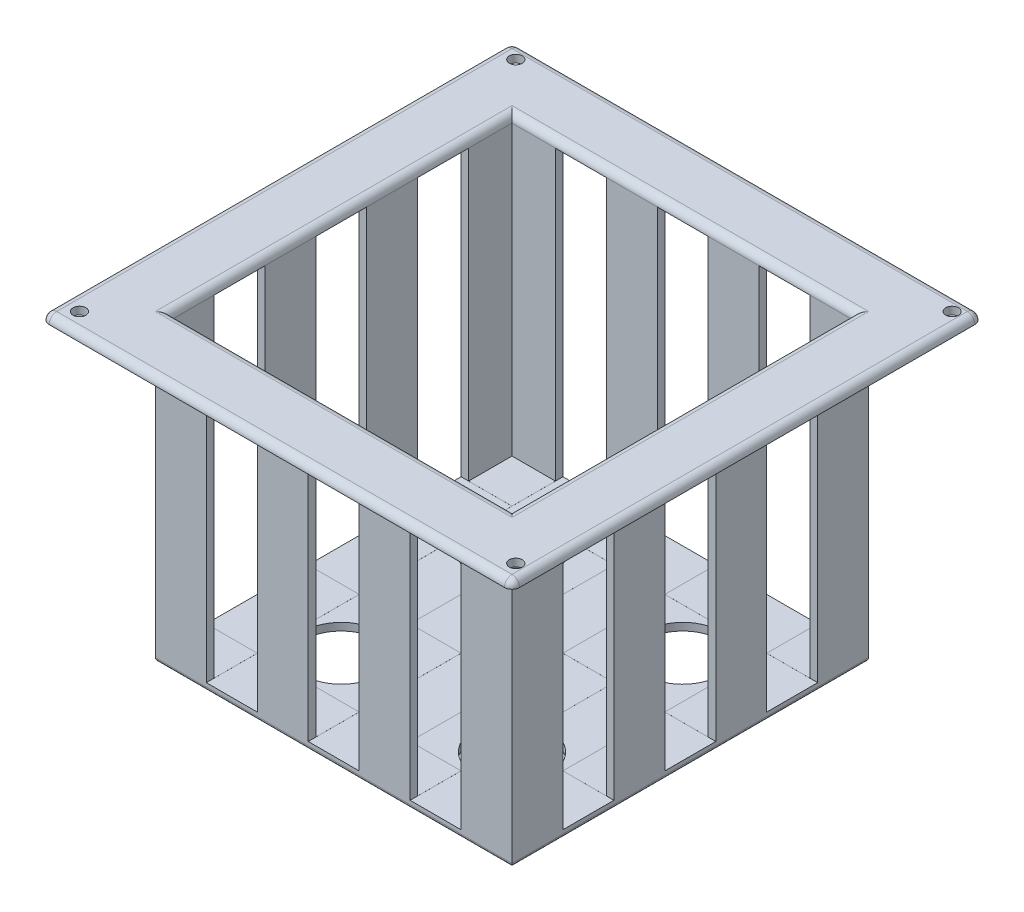
SolidWorks part; units mm, degrees
ref_plane "前视基准面" through (0, 0, 0) normal (0, 0, 1) x (1, 0, 0)
ref_plane "上视基准面" through (0, 0, 0) normal (0, 1, 0) x (1, 0, 0)
ref_plane "右视基准面" through (0, 0, 0) normal (1, 0, 0) x (0, 0, -1)
sketch "草图1" plane through (0, 0, 0) normal (0, 1, 0) x (1, 0, 0)
  line L0 (-44.8787, 74.0445) -> (49.1213, 74.0445)
  line L1 (-42.8787, 72.0445) -> (47.1213, 72.0445)
  line L2 (-42.8787, 72.0445) -> (-42.8787, -17.9555)
  line L3 (-42.8787, -17.9555) -> (47.1213, -17.9555)
  line L4 (47.1213, 72.0445) -> (47.1213, -17.9555)
  line L5 (49.1213, 74.0445) -> (49.1213, -19.9555)
  line L6 (-44.8787, -19.9555) -> (49.1213, -19.9555)
  line L7 (-44.8787, 74.0445) -> (-44.8787, -19.9555)
  line L8 (-59.8787, 89.0445) -> (64.1213, 89.0445)
  line L9 (64.1213, 89.0445) -> (64.1213, -34.9555)
  line L10 (-59.8787, -34.9555) -> (64.1213, -34.9555)
  line L11 (-59.8787, 89.0445) -> (-59.8787, -34.9555)
  dimension "D1" = 2
  dimension "D2" = 15
extrude "凸台-拉伸1" add sketch "草图1" against normal blind 80 contours L5 L6 L7 L0
extrude "切除-拉伸1" cut sketch "草图1<3>" against normal blind 78 contours L3 L4 L1 L2
sketch "草图1<3>" plane through (0, 0, 0) normal (0, 1, 0) x (1, 0, 0) same geometry as "草图1"
ref_plane "基准面4" through (0, 10, 0) normal (0, 1, 0) x (1, 0, 0)
extrude "凸台-拉伸2" add sketch "草图1<5>" against normal blind 2 contours L0 L5 L6 L7 | L8 L9 L10 L11
sketch "草图1<5>" plane through (0, 0, 0) normal (0, 1, 0) x (1, 0, 0) same geometry as "草图1"
fillet "圆角1" radius 2 4 edges at (2.1213, 0, 17.9555) (47.1213, 0, -27.0445) (2.1213, 0, -72.0445) (-42.8787, 0, -27.0445)
sketch3d "3D草图1"
  line L0 (49.1213, -80, 19.9555) -> (49.1213, -78, 19.9555) construction
  line L1 (49.1213, -80, 19.9555) -> (49.1213, -2, 19.9555) construction
  line L2 (49.1213, -78, 19.9555) -> (49.1213, -78.0094, -74.0445) construction
  line L3 (49.1213, -80, -74.0445) -> (49.1213, -2, -74.0445) construction
  line L4 (49.1213, -78.0094, -74.0445) -> (-44.8787, -78.0094, -74.0445) construction
  line L5 (-44.8787, -80, -74.0445) -> (-44.8787, -2, -74.0445) construction
  line L6 (-44.8787, -78.0094, -74.0445) -> (-44.8787, -78.0094, 19.9555) construction
  line L7 (-44.8787, -80, 19.9555) -> (-44.8787, -2, 19.9555) construction
  line L8 (-44.8787, -78.0094, 19.9555) -> (49.1213, -78, 19.9555) construction
ref_point "点1"
ref_point "点2"
ref_point "点3"
ref_point "点4"
ref_point "点5"
ref_point "点6"
sketch "草图5" plane through (49.1213, 0, 0) normal (1, 0, 0) x (0, 0, -1)
  line L0 (-19.9555, -2) -> (-6.5269, -2)
  line L1 (-6.5269, -78.0013) -> (-6.5269, -2)
  line L2 (74.0445, -2) -> (-19.9555, -2) construction
  line L3 (6.9017, -78.0027) -> (6.9017, -2)
  line L4 (20.3302, -78.004) -> (20.3302, -2)
  line L5 (33.7588, -78.0053) -> (33.7588, -2)
  line L6 (47.1874, -78.0067) -> (47.1874, -2)
  line L7 (60.616, -78.008) -> (60.616, -2)
  line L8 (-6.5269, -78.0013) -> (6.9017, -78.0027)
  line L9 (6.9017, -78.0027) -> (20.3302, -78.004)
  line L10 (20.3302, -78.004) -> (33.7588, -78.0053)
  line L11 (33.7588, -78.0053) -> (47.1874, -78.0067)
  line L12 (47.1874, -78.0067) -> (60.616, -78.008)
  line L13 (60.616, -78.008) -> (74.0445, -78.0094)
  line L14 (74.0445, -78.0094) -> (74.0445, -2)
  line L15 (74.0445, -2) -> (60.616, -2)
  line L16 (60.616, -2) -> (47.1874, -2)
  line L17 (33.7588, -2) -> (20.3302, -2)
  line L18 (20.3302, -2) -> (6.9017, -2)
  line L19 (6.9017, -2) -> (-6.5269, -2)
  line L20 (-6.5269, -2) -> (-19.9555, -2)
  line L21 (-19.9555, -2) -> (-19.9555, -78)
  line L22 (6.9017, -2) -> (20.3302, -2)
  line L23 (33.7588, -2) -> (47.1874, -2)
extrude "切除-拉伸4" cut sketch "草图5" against normal through all contours L8 L1 L19 L3
extrude "切除-拉伸5" cut sketch "草图5<5>" against normal through all contours L4 L17 L5 L10
sketch "草图5<5>" plane through (49.1213, 0, 0) normal (1, 0, 0) x (0, 0, -1) same geometry as "草图5"
extrude "切除-拉伸6" cut sketch "草图5<6>" against normal through all contours L7 L16 L6 L12
sketch "草图5<6>" plane through (49.1213, 0, 0) normal (1, 0, 0) x (0, 0, -1) same geometry as "草图5"
ref_point "点7"
ref_point "点8"
ref_point "点9"
ref_point "点10"
ref_point "点11"
ref_point "点12"
sketch "草图6" plane through (0, 0, -74.0445) normal (0, 0, -1) x (-1, 0, 0)
  line L1 (-35.6927, -78.0094) -> (-35.6927, -2)
  line L2 (44.8787, -2) -> (-49.1213, -2) construction
  line L3 (-35.6927, -2) -> (-22.2641, -2)
  line L4 (-22.2641, -2) -> (-22.2641, -78.0094)
  line L5 (-22.2641, -78.0094) -> (-8.8356, -78.0094)
  line L6 (-8.8356, -78.0094) -> (-8.8356, -2)
  line L7 (-8.8356, -2) -> (4.593, -2)
  line L8 (4.593, -2) -> (4.593, -78.0094)
  line L9 (4.593, -78.0094) -> (18.0216, -78.0094)
  line L10 (18.0216, -78.0094) -> (18.0216, -2)
  line L11 (-35.6927, -78.0094) -> (-22.2641, -78.0094)
  line L12 (-22.2641, -2) -> (-8.8356, -2)
  line L13 (4.593, -2) -> (18.0216, -2)
  line L14 (18.0216, -78.0094) -> (31.4502, -78.0094)
  line L15 (31.4502, -78.0094) -> (31.4502, -2)
  line L16 (31.4502, -2) -> (18.0216, -2)
  line L17 (4.593, -78.0094) -> (-8.8356, -78.0094)
extrude "切除-拉伸7" cut sketch "草图6" against normal through all contours L3 L4 L11 L1
extrude "切除-拉伸8" cut sketch "草图6<3>" against normal through all contours L6 L7 L8 L17
sketch "草图6<3>" plane through (0, 0, -74.0445) normal (0, 0, -1) x (-1, 0, 0) same geometry as "草图6"
extrude "切除-拉伸9" cut sketch "草图6<4>" against normal through all both and the other way through all contours L15 L16 L10 L14
sketch "草图6<4>" plane through (0, 0, -74.0445) normal (0, 0, -1) x (-1, 0, 0) same geometry as "草图6"
ref_plane "基准面6" through (0, -78, 0) normal (0, -1, 0) x (-1, 0, 0)
sketch "草图8" plane through (0, -78, 0) normal (0, -1, 0) x (-1, 0, 0)
  line L0 (-49.1213, -19.9555) -> (44.825, 73.9908) construction
  line L1 (-2.1481, 27.0177) -> (42.8787, -17.9555) construction
  line L2 (42.8787, -17.9555) -> (-2.1481, 27.0177) construction
  line L3 (-2.1481, 27.0177) -> (-47.1213, 72.0445) construction
  circle A0 centre (-2.1481, 27.0177) radius 2.5
  circle A1 centre (-2.1481, 27.0177) radius 8
  circle A2 centre (20.3653, 4.5311) radius 10
  circle A3 centre (-24.6347, 49.5311) radius 10
  circle A4 centre (-24.6347, 4.5311) radius 10
  circle A5 centre (20.3653, 49.5311) radius 10
extrude "切除-拉伸13" cut sketch "草图8" along normal through all contours A0
extrude "切除-拉伸16" cut sketch "草图8<4>" along normal blind 1 contours A1
sketch "草图8<4>" plane through (0, -78, 0) normal (0, -1, 0) x (-1, 0, 0) same geometry as "草图8"
ref_point "点13"
ref_point "点14"
ref_point "点15"
extrude "切除-拉伸17" cut sketch "草图8<5>" along normal through all contours A2 | A3 | A4 | A5
sketch "草图8<5>" plane through (0, -78, 0) normal (0, -1, 0) x (-1, 0, 0) same geometry as "草图8"
fillet "圆角2" radius 2 4 edges at (64.1213, -1, 34.9555) (-59.8787, -1, 34.9555) (64.1213, -1, -89.0445) (-59.8787, -1, -89.0445)
fillet "圆角4" radius 2 8 edges at (2.1213, 0, 34.9555) (63.5355, 0, -88.4587) (2.1213, 0, -89.0445) (-59.2929, 0, 34.3697) (-59.8787, -1, 32.9555) (-57.8787, -1, -89.0445) (64.1213, -1, -87.0445) (62.1213, -1, 34.9555) type face fillet first side face at (-59.0858, -1, -88.2516) first side face at (63.3284, -1, 34.1626) first side face at (64.1213, -1, -27.0445) first side face at (-59.8787, -1, -27.0445) first side face at (2.1213, 0, -27.0445) second side face at (63.3284, -1, -88.2516) second side face at (-59.0858, -1, 34.1626) second side face at (2.1213, -1, 34.9555) second side face at (2.1213, -1, -89.0445)
fillet "圆角10" radius 1 4 edges at (2.1213, -80, 19.9555) (2.1213, -80, -74.0445) (-44.8787, -80, -27.0445) (49.1213, -80, -27.0445) type face fillet first side face at (-20.3653, -80, -59.5311) second side face at (2.1213, -40.2535, -74.0445) second side face at (2.1213, -40.2535, 19.9555) second side face at (-44.8787, -40.2518, -27.0445) second side face at (49.1213, -40.2518, -27.0445)
sketch "草图10" plane through (0, -7, 0) normal (0, -1, 0) x (1, 0, 0)
  circle A0 centre (60.1213, 29.9555) radius 1.7
  circle A1 centre (60.1213, -85.0445) radius 1.7
  circle A2 centre (-54.8787, -85.0445) radius 1.7
  circle A3 centre (-54.8787, 29.9555) radius 1.7
extrude "切除-拉伸18" cut sketch "草图10" against normal blind 10
